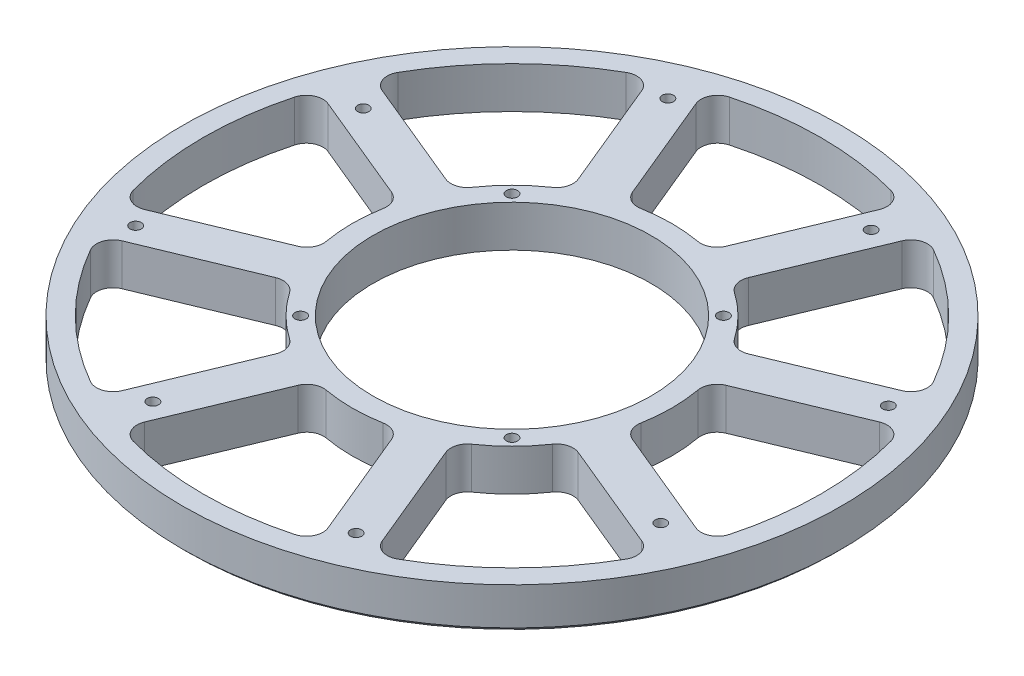
SolidWorks part; units mm, degrees
material "6061-T6 (SS)"
ref_plane "Front Plane" through (0, 0, 0) normal (0, 0, 1) x (1, 0, 0)
ref_plane "Top Plane" through (0, 0, 0) normal (0, 1, 0) x (1, 0, 0)
ref_plane "Right Plane" through (0, 0, 0) normal (1, 0, 0) x (0, 0, -1)
sketch "Sketch2" plane through (0, 0, 0) normal (1, 0, 0) x (0, 0, -1)
  line L0 (0, 0) -> (-79.375, 0)
  line L1 (-79.375, 0) -> (-79.375, 10)
  line L2 (-79.375, 10) -> (0, 10)
  line L5 (0, 10) -> (0, 0)
  dimension "D1" = 79.375
  dimension "D2" = 10
ref_axis "Axis1" through (0, -0.5, 0) along (0, 1, 0)
revolve "Revolve1" add sketch "Sketch2" angle 360 about axis through (0, -0.5, 0) along (0, 1, 0)
hole_wizard "#6-32 Tapped Hole1" positions "Sketch6" profile "Sketch7" tap size "#6-32" standard "ANSI Inch" end condition through all
sketch "Sketch6" plane through (0, 10, 0) normal (0, 1, 0) x (1, 0, 0)
  line L0 (0, 0) -> (-53.438, 129.0108) construction
  line L2 (0, 0) -> (0, 109.0908) construction
  line L3 (0, 0) -> (-73.3329, 30.3755) construction
  line L4 (0, 0) -> (-68.4315, 68.4315) construction
  circle A0 centre (0, 0) radius 79.375 construction
  point P0 (-26.5487, 64.0941)
  point P18 (-61.1608, 25.3336)
  point P27 (-25.4558, 25.4558)
  dimension "D1" = 22.5
  dimension "D2" = 69.375
  dimension "D3" = 45
  dimension "D4" = 66.2
  dimension "D6" = 22.5
  dimension "D5" = 36
sketch "Sketch7" plane through (-26.5487, 10, -64.0941) normal (1, 0, 0) x (0, 0, 1)
  line L0 (0, 0) -> (0, 10)
  line L1 (0, 10) -> (1.3525, 10)
  line L2 (1.3525, 10) -> (1.3525, 0)
  line L5 (1.3525, 0) -> (0, 0)
  line L11 (0, -6.35) -> (0, 107.95) construction
  dimension "Thread Major Dia." = 2.7051
  dimension "Thru Tap Drill Depth" = 10
pattern_circular "CirPattern3" count 4 over 360 about axis through (0, -0.5, 0) along (0, 1, 0) of "#6-32 Tapped Hole1"
sketch "Sketch8" plane through (0, 10, 0) normal (0, 1, 0) x (1, 0, 0)
  line L4 (0, 0) -> (0, 93.9995) construction
  line L5 (0, 0) -> (113.8372, 0) construction
  line L6 (-9.9891, 37.1815) -> (-23.7783, 70.4715)
  line L7 (9.9891, 37.1815) -> (23.7783, 70.4715)
  line L8 (0, 0) -> (-26.5487, 64.0941) construction
  arc A0 (-9.9891, 37.1815) -> (9.9891, 37.1815) centre (0, 0) cw
  arc A1 (-23.7783, 70.4715) -> (23.7783, 70.4715) centre (0, 0) cw
  circle A2 centre (0, 0) radius 79.375 construction
  dimension "D1" = 38.5
  dimension "D2" = 5
  dimension "D3" = 5
extrude "Cut-Extrude1" cut sketch "Sketch8" against normal through all
fillet "Fillet1" radius 4 4 edges at (9.9891, 5, -37.1815) (23.7783, 5, -70.4715) (-9.9891, 5, -37.1815) (-23.7783, 5, -70.4715)
pattern_circular "CirPattern4" count 8 over 360 about axis through (0, -0.5, 0) along (0, 1, 0) of "Cut-Extrude1", "Fillet1"
chamfer "Chamfer2" distance 1 angle 45 1 edges at (0, 0, -79.375)
sketch "Sketch9" plane through (0, 10, 0) normal (0, 1, 0) x (1, 0, 0)
  circle A0 centre (0, 0) radius 33.5
  dimension "D1" = 67
extrude "Cut-Extrude2" cut sketch "Sketch9" against normal through all
equation "\"TubeDiameter\" = 6.250in"
equation "\"D1@Sketch2\"=\"TubeDiameter\"/2"
equation "\"D2@Sketch6\"=\"TubeDiameter\"/2-10mm"
